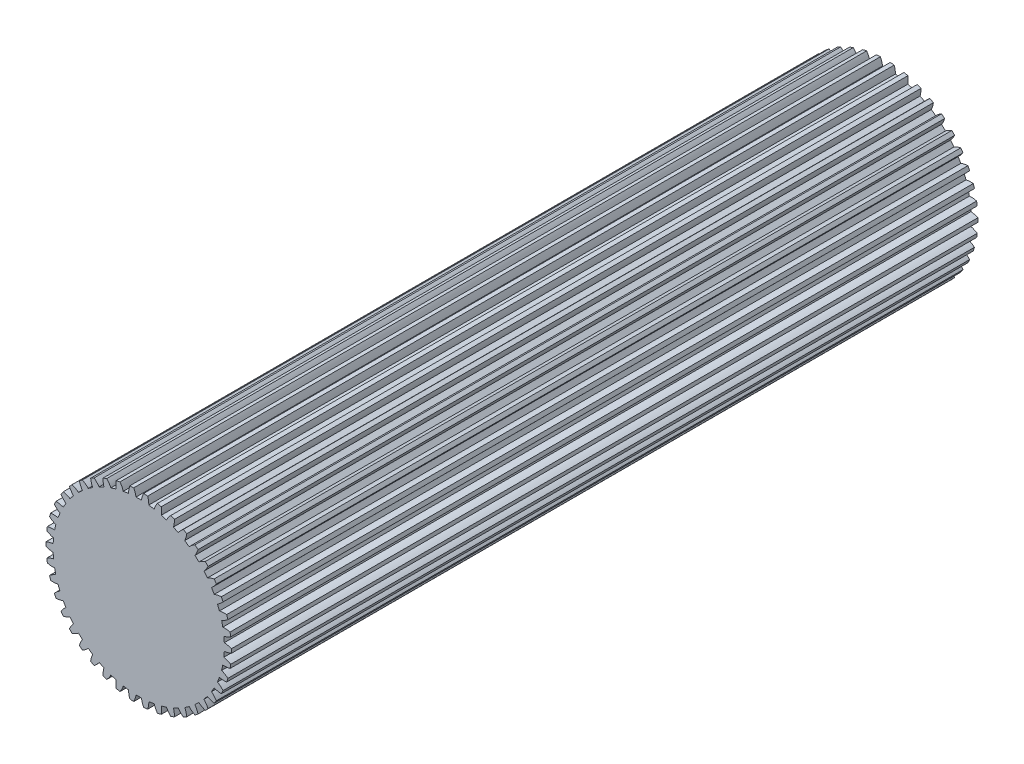
SolidWorks part; units mm, degrees
material "Brass"
ref_plane "Front Plane" through (0, 0, 0) normal (0, 0, 1) x (1, 0, 0)
ref_plane "Top Plane" through (0, 0, 0) normal (0, 1, 0) x (1, 0, 0)
ref_plane "Right Plane" through (0, 0, 0) normal (1, 0, 0) x (0, 0, -1)
sketch "Sketch1" plane through (0, 0, 0) normal (0, 0, 1) x (1, 0, 0)
  circle A0 centre (0, 0) radius 18.6267
  dimension "D1" = 37.2533
extrude "Boss-Extrude1" add sketch "Sketch1" along normal blind 150
sketch "Sketch2" plane through (0, 0, 0) normal (0, 0, 1) x (1, 0, 0)
  spline S0 degree 4 poles (17.1978, 0.739) (17.2039, 0.7392) (17.2154, 0.7393) (17.2343, 0.7391) (17.2715, 0.7379) (17.3137, 0.7353) (17.3614, 0.7312) (17.4127, 0.7257) (17.4566, 0.7203) (17.5005, 0.7141) (17.5443, 0.7075) (17.5973, 0.6986) (17.661, 0.6871) (17.7355, 0.6721) (17.8202, 0.6533) (17.9066, 0.6324) (17.9918, 0.6103) (18.078, 0.5862) (18.1615, 0.5616) (18.2484, 0.5343) (18.3286, 0.5082) (18.4188, 0.4769) (18.4915, 0.451) (18.5877, 0.4148) (18.6446, 0.3928) (18.7113, 0.3663) (18.7409, 0.3541) (18.7591, 0.3466) knots 0 0 0 0 0 0.015084 0.028532 0.04661 0.092111 0.119476 0.146842 0.174209 0.201575 0.228941 0.256307 0.307035 0.361767 0.4165 0.471232 0.525964 0.580697 0.635429 0.690161 0.744894 0.799626 0.854358 0.909091 0.954545 1 1 1 1 1 construction
  spline S1 degree 4 poles (17.1978, 0.739) (17.2039, 0.7392) (17.2154, 0.7393) (17.2343, 0.7391) (17.2715, 0.7379) (17.3137, 0.7353) (17.3614, 0.7312) (17.4127, 0.7257) (17.4566, 0.7203) (17.5005, 0.7141) (17.5443, 0.7075) (17.5973, 0.6986) (17.661, 0.6871) (17.7355, 0.6721) (17.8202, 0.6533) (17.9066, 0.6324) (17.9918, 0.6103) (18.078, 0.5862) (18.1615, 0.5616) (18.2484, 0.5343) (18.3286, 0.5082) (18.4188, 0.4769) (18.4915, 0.451) (18.5669, 0.4227) (18.6036, 0.4086) (18.6223, 0.4013) knots 0 0 0 0 0 0.015084 0.028532 0.04661 0.092111 0.119476 0.146842 0.174209 0.201575 0.228941 0.256307 0.307035 0.361767 0.4165 0.471232 0.525964 0.580697 0.635429 0.690161 0.744894 0.799626 0.854358 0.909091 0.909091 0.909091 0.909091 0.909091
  spline S2 degree 4 poles (17.1159, 1.8324) (17.1219, 1.8331) (17.1333, 1.8348) (17.152, 1.8378) (17.1886, 1.8446) (17.2299, 1.8534) (17.2765, 1.8645) (17.3264, 1.8776) (17.369, 1.8896) (17.4115, 1.9022) (17.4538, 1.9153) (17.5049, 1.9319) (17.5661, 1.9529) (17.6376, 1.9788) (17.7185, 2.0099) (17.8009, 2.0435) (17.8818, 2.0781) (17.9634, 2.1148) (18.0423, 2.1515) (18.1242, 2.1915) (18.1997, 2.2293) (18.2841, 2.2736) (18.3522, 2.31) (18.442, 2.3602) (18.4949, 2.3904) (18.5569, 2.4266) (18.5843, 2.4431) (18.6013, 2.4532) knots 0 0 0 0 0 0.015084 0.028532 0.04661 0.092111 0.119476 0.146842 0.174209 0.201575 0.228941 0.256307 0.307035 0.361767 0.4165 0.471232 0.525964 0.580697 0.635429 0.690161 0.744894 0.799626 0.854358 0.909091 0.954545 1 1 1 1 1 construction
  spline S3 degree 4 poles (17.1159, 1.8324) (17.1219, 1.8331) (17.1333, 1.8348) (17.152, 1.8378) (17.1886, 1.8446) (17.2299, 1.8534) (17.2765, 1.8645) (17.3264, 1.8776) (17.369, 1.8896) (17.4115, 1.9022) (17.4538, 1.9153) (17.5049, 1.9319) (17.5661, 1.9529) (17.6376, 1.9788) (17.7185, 2.0099) (17.8009, 2.0435) (17.8818, 2.0781) (17.9634, 2.1148) (18.0423, 2.1515) (18.1242, 2.1915) (18.1997, 2.2293) (18.2841, 2.2736) (18.3522, 2.31) (18.4225, 2.3493) (18.4567, 2.3687) (18.4742, 2.3787) knots 0 0 0 0 0 0.015084 0.028532 0.04661 0.092111 0.119476 0.146842 0.174209 0.201575 0.228941 0.256307 0.307035 0.361767 0.4165 0.471232 0.525964 0.580697 0.635429 0.690161 0.744894 0.799626 0.854358 0.909091 0.909091 0.909091 0.909091 0.909091
  spline S4 degree 1 poles (17.1159, 1.8324) (17.1978, 0.739) knots 0 0 1 1 construction
  spline S5 degree 1 poles (17.1159, 1.8324) (17.1978, 0.739) knots 0 0 1 1
  spline S6 degree 1 poles (18.6223, 0.4013) (59.9861, 1.2927) knots 0 0 1 1 construction
  spline S7 degree 1 poles (18.6223, 0.4013) (59.9861, 1.2927) knots 0 0 1 1
  spline S8 degree 4 poles (59.9965, 0.6495) (59.996, 0.6954) (59.9948, 0.7841) (59.9935, 0.9041) (59.9876, 1.2291) (59.9845, 1.3714) (59.9739, 1.7905) (59.9657, 2.0284) (59.9537, 2.3723) (59.9415, 2.6523) (59.9269, 2.9708) (59.9113, 3.2659) (59.8938, 3.5749) (59.875, 3.8756) (59.8545, 4.1808) (59.8325, 4.4838) (59.8091, 4.7868) (59.7838, 5.0915) (59.7577, 5.3917) (59.7289, 5.6999) (59.7003, 5.9941) (59.6673, 6.3111) (59.6376, 6.5899) (59.5983, 6.9317) (59.5709, 7.1681) (59.5189, 7.5842) (59.5007, 7.7253) (59.4582, 8.0476) (59.4416, 8.1664) (59.4295, 8.2543) (59.4232, 8.2997) knots 0 0 0 0 0 0.020959 0.041918 0.083333 0.123016 0.162698 0.202381 0.242063 0.281746 0.321429 0.361111 0.400794 0.440476 0.480159 0.519841 0.559524 0.599206 0.638889 0.678571 0.718254 0.757937 0.797619 0.837302 0.876984 0.916667 0.958082 0.979041 1 1 1 1 1 construction
  spline S9 degree 4 poles (59.9861, 1.2927) (59.9847, 1.3561) (59.9818, 1.4796) (59.9739, 1.7905) (59.9657, 2.0284) (59.9537, 2.3723) (59.9415, 2.6523) (59.9269, 2.9708) (59.9113, 3.2659) (59.8938, 3.5749) (59.875, 3.8756) (59.8545, 4.1808) (59.8325, 4.4838) (59.8091, 4.7868) (59.7838, 5.0915) (59.7577, 5.3917) (59.7289, 5.6999) (59.7003, 5.9941) (59.6673, 6.3111) (59.6376, 6.5899) (59.5983, 6.9317) (59.5709, 7.1681) (59.5324, 7.4768) (59.5168, 7.5993) (59.5087, 7.6622) knots 0.083333 0.083333 0.083333 0.083333 0.083333 0.123016 0.162698 0.202381 0.242063 0.281746 0.321429 0.361111 0.400794 0.440476 0.480159 0.519841 0.559524 0.599206 0.638889 0.678571 0.718254 0.757937 0.797619 0.837302 0.876984 0.916667 0.916667 0.916667 0.916667 0.916667
  spline S10 degree 1 poles (59.5087, 7.6622) (18.4742, 2.3787) knots 0 0 1 1 construction
  spline S11 degree 1 poles (59.5087, 7.6622) (18.4742, 2.3787) knots 0 0 1 1
extrude "Cut-Extrude2" cut sketch "Sketch2" against normal blind 151 and the other way blind 151
ref_axis "Axis1" through (0, 0, -7.5) along (0, 0, 1)
pattern_circular "CirPattern1" count 42 over 360 about axis through (0, 0, -7.5) along (0, 0, 1) of "Cut-Extrude2"
